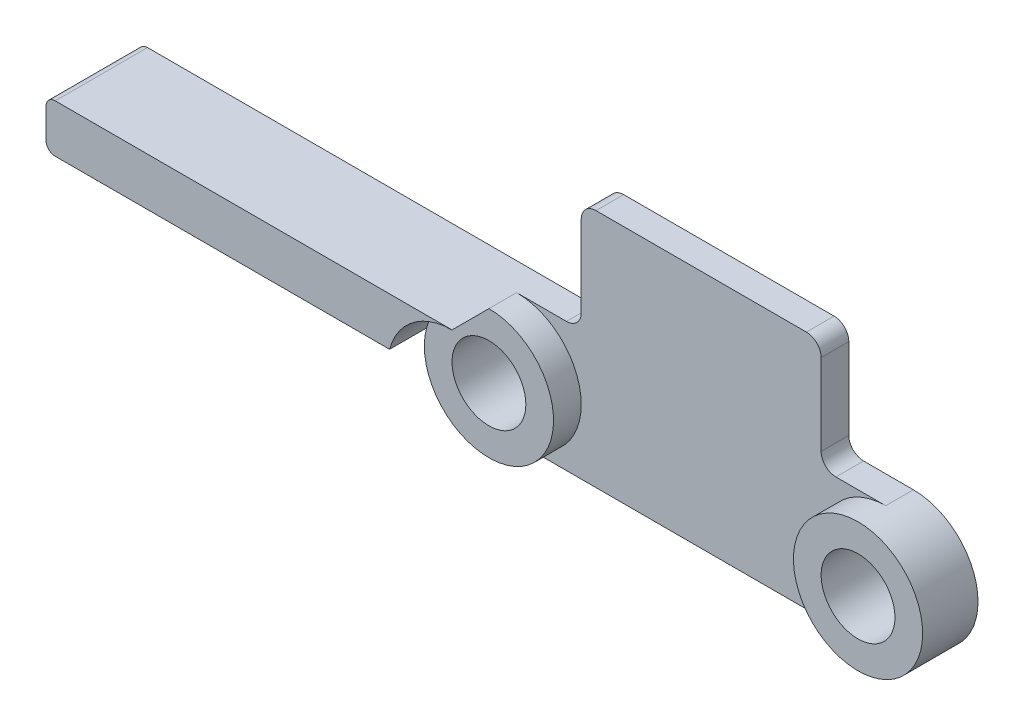
SolidWorks part; units mm, degrees
note: The reader was unsure of these and kept them because the rebuilt part matched: shared geometry of "Sketch1<3>".
ref_plane "Front Plane" through (0, 0, 0) normal (0, 0, 1) x (1, 0, 0)
ref_plane "Top Plane" through (0, 0, 0) normal (0, 1, 0) x (1, 0, 0)
ref_plane "Right Plane" through (0, 0, 0) normal (1, 0, 0) x (0, 0, -1)
sketch "Sketch1" plane through (0, 0, 0) normal (0, 0, 1) x (1, 0, 0)
  line L0 (0, 0) -> (20, 0) construction
  line L1 (0, 3.5) -> (20, 3.5)
  line L2 (0, -3.5) -> (20, -3.5)
  line L4 (3.5, -3.5) -> (16.5, -3.5)
  line L5 (3.5, -3.5) -> (3.5, 9.5)
  line L6 (3.5, 9.5) -> (16.5, 9.5)
  line L7 (16.5, -3.5) -> (16.5, 9.5)
  line L8 (0, 0.8982) -> (-22, 0.8982)
  line L9 (0, 0.8982) -> (0, 3.5)
  line L10 (0, 3.5) -> (-22, 3.5)
  line L11 (-22, 0.8982) -> (-22, 3.5)
  arc A0 (0, 3.5) -> (0, -3.5) centre (0, 0) ccw
  arc A1 (20, -3.5) -> (20, 3.5) centre (20, 0) ccw
  circle A2 centre (0, 0) radius 2
  circle A3 centre (20, 0) radius 2
  point P3 (10, 0)
  point P12 (10, 9.5)
  point P13 (10, -3.5)
  dimension "D4" = 4
  dimension "D5" = 4
  dimension "D1" = 20
  dimension "D2" = 7
  dimension "D3" = 13
  dimension "D6" = 22
extrude "Boss-Extrude1" add sketch "Sketch1" along normal blind 1.5
extrude "Boss-Extrude2" add sketch "Sketch1<3>" along normal blind 5 contours A0 L10 L11 L8
sketch "Sketch1<3>" plane through (0, 0, 0) normal (0, 0, 1) x (1, 0, 0) same geometry as "Sketch1"
sketch "Sketch2" plane through (0, 0, 1.5) normal (0, 0, 1) x (1, 0, 0)
  circle A0 centre (20, 0) radius 3.5
  circle A1 centre (0, 0) radius 3.5
  circle A3 centre (20, 0) radius 2 construction
  circle A4 centre (0, 0) radius 2
  circle A5 centre (20, 0) radius 2
  dimension "D1" = 7
extrude "Boss-Extrude3" add sketch "Sketch2" along normal blind 1.5
fillet "Fillet2" radius 0.8 4 edges at (16.5, 9.5, 0.75) (16.5, 3.5, 0.75) (3.5, 9.5, 0.75) (3.5, 3.5, 0.75)
fillet "Fillet3" radius 0.5 2 edges at (-22, 3.5, 2.5) (-22, 0.8982, 2.5)
